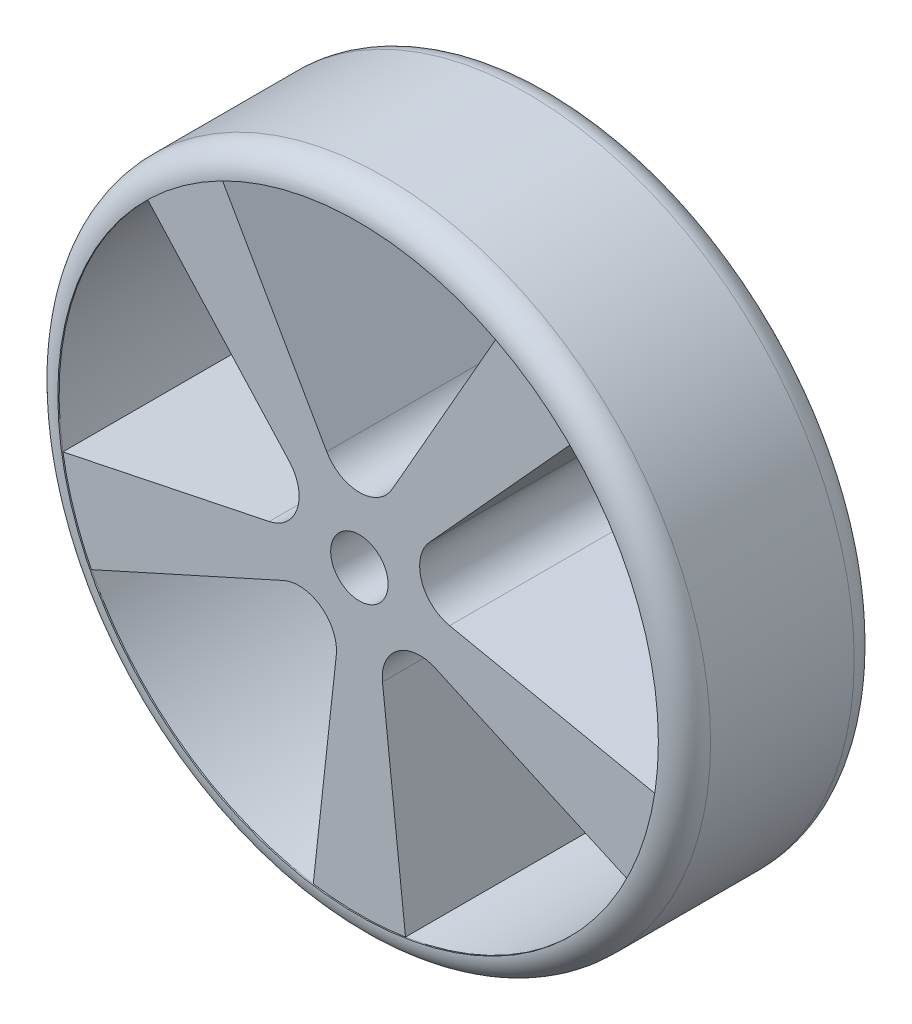
SolidWorks part; units mm, degrees
ref_plane "Front Plane" through (0, 0, 0) normal (0, 0, 1) x (1, 0, 0)
ref_plane "Top Plane" through (0, 0, 0) normal (0, 1, 0) x (1, 0, 0)
ref_plane "Right Plane" through (0, 0, 0) normal (1, 0, 0) x (0, 0, -1)
sketch "Sketch1" plane through (0, 0, 0) normal (0, 0, 1) x (1, 0, 0)
  line L0 (0, 0) -> (0, 25)
  circle A0 centre (0, 0) radius 25
  dimension "D1" = 50
extrude "Boss-Extrude1" add sketch "Sketch1" along normal blind 15 contours A0
fillet "Fillet1" radius 2 2 edges at (25, 0, 15) (25, 0, 0)
sketch "Sketch7" plane through (0, 0, 15) normal (0, 0, 1) x (1, 0, 0)
  circle A0 centre (0, 0) radius 2.2
  dimension "D1" = 4.4
extrude "Cut-Extrude2" cut sketch "Sketch7" along normal through all and the other way through all
ref_plane "Plane1" through (0, 0, 7.5) normal (0, 0, -1) x (-1, 0, 0)
sketch "Sketch8" plane through (0, 0, 15) normal (0, 0, 1) x (1, 0, 0)
  circle A0 centre (0, 0) radius 23
  dimension "D1" = 46
extrude "Cut-Extrude3" cut sketch "Sketch8" against normal blind 0.1
sketch "Sketch9" plane through (0, 0, 0) normal (0, 0, -1) x (-1, 0, 0)
  circle A0 centre (0, 0) radius 23
  dimension "D1" = 46
extrude "Cut-Extrude4" cut sketch "Sketch9" against normal blind 0.1
sketch "Sketch10" plane through (0, 0, 0.1) normal (0, 0, -1) x (-1, 0, 0)
  circle A0 centre (0, 0) radius 23
  dimension "D1" = 46
extrude "Boss-Extrude3" add sketch "Sketch10" against normal blind 0.1
sketch "Sketch11" plane through (0, 0, 7.5) normal (0, 0, -1) x (-1, 0, 0)
  circle A0 centre (0, 0) radius 2.2
  dimension "D1" = 4.4
extrude "Cut-Extrude5" cut sketch "Sketch11" along normal through all
sketch "Sketch12" plane through (0, 0, 14.9) normal (0, 0, 1) x (1, 0, 0)
  circle A0 centre (0, 0) radius 23
  dimension "D1" = 46
extrude "Boss-Extrude4" add sketch "Sketch12" against normal blind 0.1
sketch "Sketch13" plane through (0, 0, 0.1) normal (0, 0, -1) x (-1, 0, 0)
  circle A0 centre (0, 0) radius 2.2
extrude "Cut-Extrude6" cut sketch "Sketch13" against normal through all
sketch "Sketch14" plane through (0, 0, 14.9) normal (0, 0, 1) x (1, 0, 0)
  line L0 (-2.5, 6.4514) -> (-10.5, 20.4634)
  line L1 (2.5, 6.4514) -> (10.5, 20.4634)
  circle A1 centre (0, 0) radius 23 construction
  arc A3 (-2.5, 6.4514) -> (2.5, 6.4514) centre (0, 7.8788) ccw
  arc A4 (10.5, 20.4634) -> (-10.5, 20.4634) centre (0, 2.0727) ccw
  circle A5 centre (0, 0) radius 23 construction
  point P1 (0, 5)
  point P9 (-2.7249, 22.838)
  point P14 (-2.589, 5.9853)
  point P15 (-5.8301, 22.2488)
  point P16 (-0.9529, 5.8012)
  point P17 (-2.4294, 22.8713)
  point P18 (2.7419, 5.7627)
  point P19 (4.6031, 22.5347)
  point P20 (5.7156, 22.2785)
  point P21 (-1.7563, 6.078)
  point P22 (4.8749, 22.4774)
  point P23 (2.8475, 6.4348)
  point P24 (-5.4314, 7.3062)
  point P25 (-11.2414, 20.0657)
  point P26 (-3.3296, 7.2809)
  point P27 (-7.9979, 21.5646)
  point P28 (-1.8226, 6.5866)
  point P29 (-2.8195, 22.8265)
  point P30 (4.7053, 8.3951)
  point P31 (-10.5649, 20.4299)
  point P32 (8.7197, 21.283)
  point P33 (-4.0071, 7.6682)
  dimension "D1" = 5
  dimension "D2" = 5
  dimension "D3" = 21
extrude "Cut-Extrude7" cut sketch "Sketch14" against normal through all
pattern_circular "CirPattern1" count 5 over 360 about axis through (0, 0, 15) along (0, 0, -1) of "Cut-Extrude7"
